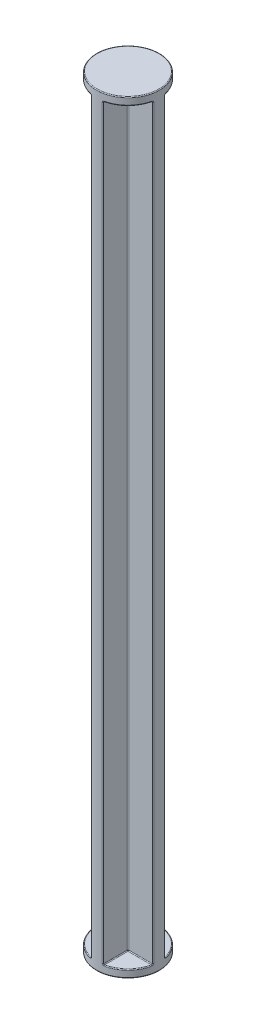
SolidWorks part; units mm, degrees
ref_plane "Front Plane" through (0, 0, 0) normal (0, 0, 1) x (1, 0, 0)
ref_plane "Top Plane" through (0, 0, 0) normal (0, 1, 0) x (1, 0, 0)
ref_plane "Right Plane" through (0, 0, 0) normal (1, 0, 0) x (0, 0, -1)
sketch "Sketch1" plane through (0, 0, 0) normal (0, 1, 0) x (1, 0, 0)
  circle A0 centre (0, 0) radius 4
  dimension "D1" = 8
extrude "Boss-Extrude1" add sketch "Sketch1" along normal blind 97
sketch "Sketch2" plane through (0, 97, 0) normal (0, 1, 0) x (1, 0, 0)
  line L0 (-0.75, 0.75) -> (-0.75, 3.9291)
  line L1 (-0.75, -0.75) -> (-3.9291, -0.75)
  line L2 (-0.75, 0.75) -> (-3.9291, 0.75)
  line L3 (0.75, 0.75) -> (0.75, 3.9291)
  line L4 (0.75, 0.75) -> (3.9291, 0.75)
  line L5 (0.75, -0.75) -> (3.9291, -0.75)
  line L6 (0.75, -0.75) -> (0.75, -3.9291)
  line L7 (-0.75, -0.75) -> (-0.75, -3.9291)
  arc A0 (3.9291, 0.75) -> (0.75, 3.9291) centre (0, 0) ccw
  circle A1 centre (0, 0) radius 4
  arc A2 (-0.75, 3.9291) -> (-3.9291, 0.75) centre (0, 0) ccw
  arc A3 (0.75, -3.9291) -> (3.9291, -0.75) centre (0, 0) ccw
  arc A4 (-3.9291, -0.75) -> (-0.75, -3.9291) centre (0, 0) ccw
  dimension "D2" = 1.5
  dimension "D3" = 1.5
  dimension "D4" = 1.5
  dimension "D5" = 1.5
  dimension "D6" = 0.75
  dimension "D7" = 0.75
  dimension "D8" = 0.75
  dimension "D1" = 0
extrude "Cut-Extrude1" cut sketch "Sketch2" against normal blind 95 from offset 1 offset against normal yes
fillet "Fillet1" radius 0.1 38 edges at (-2.8284, 96, 2.8284) (-2.8284, 96, -2.8284) (2.8284, 96, -2.8284) (-0.75, 48.5, 3.9291) (-0.75, 96, 2.3395) (-0.75, 48.5, 0.75) (-3.9291, 48.5, 0.75) (-2.3395, 96, 0.75) (-2.8284, 1, 2.8284) (-2.3395, 1, 0.75) (-0.75, 1, 2.3395) (0.75, 1, 2.3395) (0.75, 96, 2.3395) (2.3395, 1, 0.75) (0.75, 48.5, 0.75) (2.3395, 96, 0.75) (0, 0, 4) (3.9291, 48.5, 0.75) (2.8284, 96, 2.8284) (0.75, 48.5, 3.9291) (2.8284, 1, 2.8284) (-3.9291, 48.5, -0.75) (-2.3395, 96, -0.75) (-0.75, 48.5, -0.75) (-0.75, 48.5, -3.9291) (-0.75, 96, -2.3395) (-2.8284, 1, -2.8284) (-0.75, 1, -2.3395) (-2.3395, 1, -0.75) (3.9291, 48.5, -0.75) (2.3395, 96, -0.75) (0.75, 48.5, -3.9291) (0.75, 48.5, -0.75) (0.75, 96, -2.3395) (0.75, 1, -2.3395) (2.8284, 1, -2.8284) (2.3395, 1, -0.75) (0, 97, 4)
